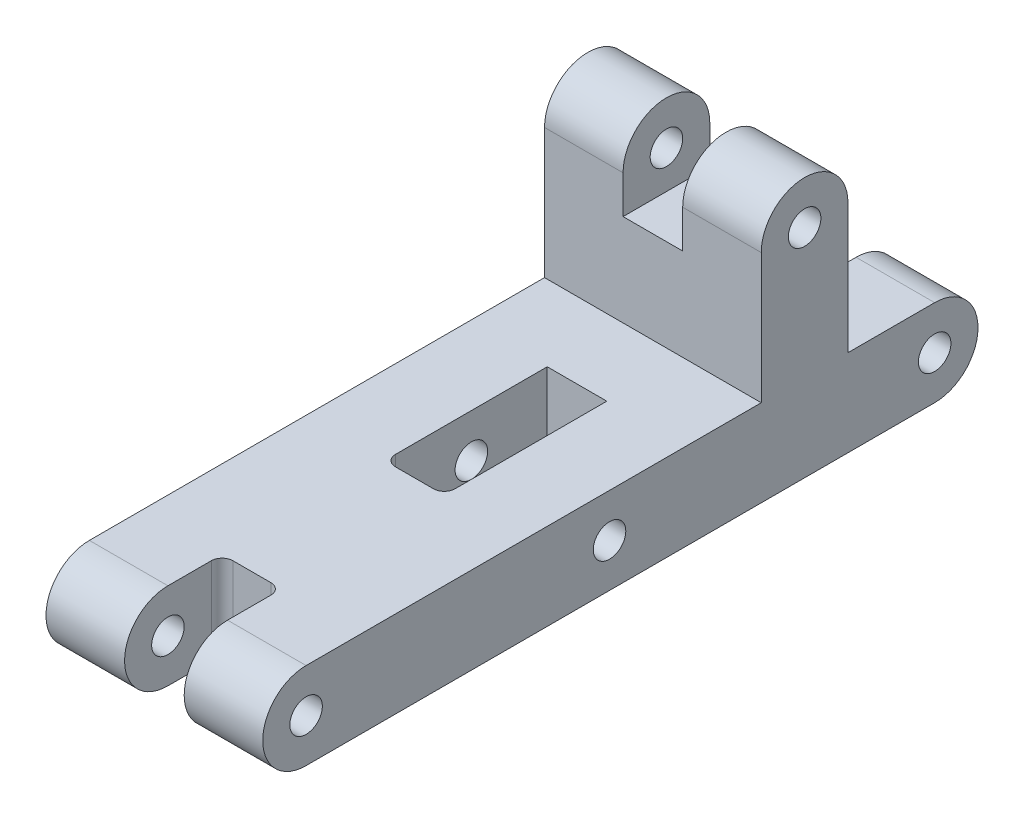
SolidWorks part; units mm, degrees
ref_plane "Alzado" through (0, 0, 0) normal (0, 0, 1) x (1, 0, 0)
ref_plane "Planta" through (0, 0, 0) normal (0, 1, 0) x (1, 0, 0)
ref_plane "Vista lateral" through (0, 0, 0) normal (1, 0, 0) x (0, 0, -1)
sketch "Croquis1" plane through (0, 0, 0) normal (1, 0, 0) x (0, 0, -1)
  line L0 (-15, 0) -> (15, 0) construction
  line L1 (-15, 4) -> (-1, 4)
  line L2 (-15, -4) -> (15, -4)
  line L3 (7, 4) -> (15, 4)
  line L5 (-1, 4) -> (-1, 16)
  line L6 (-1, 16) -> (7, 16) construction
  line L7 (7, 4) -> (7, 16)
  line L8 (-15, 4) -> (-43, 4)
  line L9 (-15, -4) -> (-43, -4)
  line L10 (-43, 4) -> (-43, -4) construction
  arc A0 (-15, 4) -> (-15, -4) centre (-15, 0) ccw construction
  arc A1 (15, -4) -> (15, 4) centre (15, 0) ccw
  circle A2 centre (15, 0) radius 1.5
  arc A3 (7, 16) -> (-1, 16) centre (3, 16) ccw
  circle A4 centre (3, 16) radius 1.5
  circle A5 centre (-15, 0) radius 1.5
  arc A6 (-43, 4) -> (-43, -4) centre (-43, 0) ccw
  circle A7 centre (-43, 0) radius 1.5
  point P3 (0, 0)
  dimension "D2" = 4
  dimension "D3" = 3
  dimension "D4" = 4
  dimension "D7" = 28
  dimension "D1" = 30
  dimension "D5" = 8
  dimension "D6" = 12
extrude "Saliente-Extruir1" add sketch "Croquis1" along normal mid plane 20
sketch "Croquis2" plane through (0, 0, 0) normal (1, 0, 0) x (0, 0, -1)
  line L0 (-1, 16) -> (-1, 4) construction
  line L1 (-1, 12.5) -> (7, 12.5)
  line L2 (-1, 12.5) -> (-1, 20)
  line L3 (-1, 20) -> (7, 20)
  line L4 (7, 12.5) -> (7, 20)
  line L5 (7, 4) -> (7, 16) construction
  line L6 (-1, 4) -> (-43, 4) construction
  line L7 (-8, 4) -> (-23, 4)
  line L8 (-8, 4) -> (-8, -4)
  line L9 (-8, -4) -> (-23, -4)
  line L10 (-23, 4) -> (-23, -4)
  line L11 (-43, -4) -> (15, -4) construction
  line L12 (15, 4) -> (7, 4) construction
  line L13 (10, 4) -> (19, 4)
  line L14 (10, 4) -> (10, -4)
  line L15 (10, -4) -> (19, -4)
  line L16 (19, 4) -> (19, -4)
  line L17 (-1, 4) -> (-43, 4) construction
  line L18 (-38, 4) -> (-47, 4)
  line L19 (-38, 4) -> (-38, -4)
  line L20 (-38, -4) -> (-47, -4)
  line L21 (-47, 4) -> (-47, -4)
  line L22 (-43, -4) -> (15, -4) construction
  arc A0 (7, 16) -> (-1, 16) centre (3, 16) ccw construction
  arc A2 (15, -4) -> (15, 4) centre (15, 0) ccw construction
  circle A4 centre (-15, 0) radius 1.5 construction
  arc A5 (-43, 4) -> (-43, -4) centre (-43, 0) ccw construction
  dimension "D5" = 9
  dimension "D1" = 7.5
  dimension "D2" = 8
  dimension "D3" = 9
  dimension "D4" = 8
extrude "Cortar-Extruir1" cut sketch "Croquis2" against normal mid plane 5.5
fillet "Redondeo1" radius 1 6 edges at (2.75, 0, 23) (-2.75, 0, 23) (2.75, 0, 38) (-2.75, 0, 38) (2.75, 0, -10) (-2.75, 0, -10)
